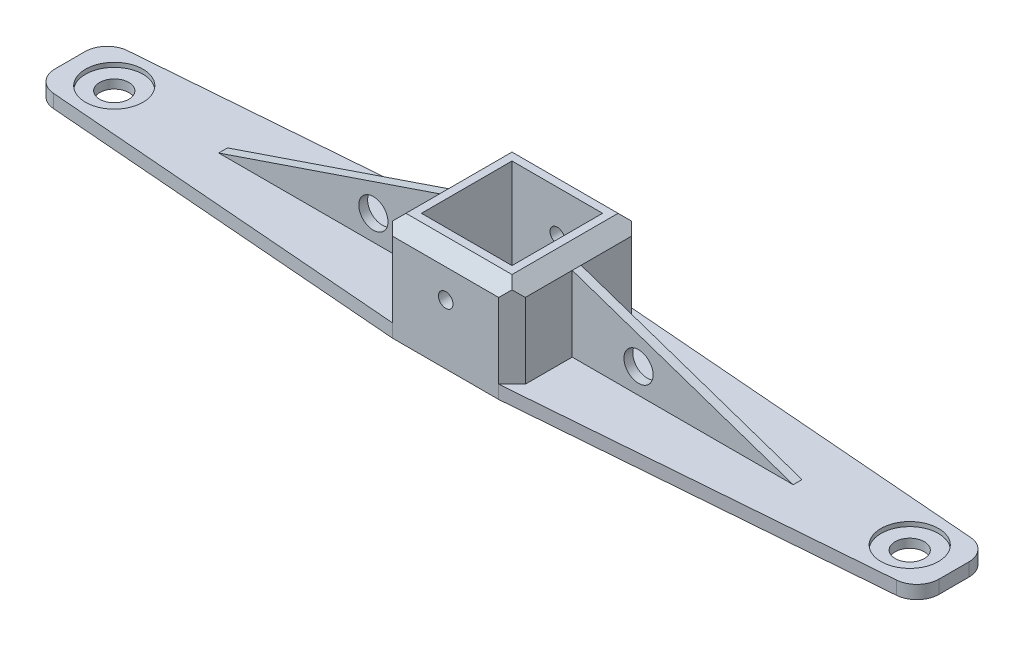
SolidWorks part; units mm, degrees
ref_plane "Front Plane" through (0, 0, 0) normal (0, 0, 1) x (1, 0, 0)
ref_plane "Top Plane" through (0, 0, 0) normal (0, 1, 0) x (1, 0, 0)
ref_plane "Right Plane" through (0, 0, 0) normal (1, 0, 0) x (0, 0, -1)
sketch "Sketch1" plane through (0, 0, 0) normal (0, 1, 0) x (1, 0, 0)
  line L1 (-100, 15) -> (100, 15)
  line L2 (-100, 15) -> (-100, -15)
  line L3 (-100, -15) -> (100, -15)
  line L4 (100, 15) -> (100, -15)
  line L5 (-100, 15) -> (100, -15) construction
  line L6 (-100, -15) -> (100, 15) construction
  point P0 (0, 0)
  dimension "D1" = 200
  dimension "D2" = 30
extrude "Boss-Extrude1" add sketch "Sketch1" along normal blind 3
sketch "Sketch2" plane through (0, 3, 0) normal (0, 1, 0) x (1, 0, 0)
  line L1 (-10.25, 10.25) -> (10.25, 10.25)
  line L2 (-10.25, 10.25) -> (-10.25, -10.25)
  line L3 (-10.25, -10.25) -> (10.25, -10.25)
  line L4 (10.25, 10.25) -> (10.25, -10.25)
  line L5 (-10.25, 10.25) -> (10.25, -10.25) construction
  line L6 (-10.25, -10.25) -> (10.25, 10.25) construction
  point P0 (0, 0)
  dimension "D1" = 20.5
  dimension "D2" = 20.5
extrude "Cut-Extrude1" cut sketch "Sketch2" against normal blind 3
sketch "Sketch3" plane through (0, 3, 0) normal (0, 1, 0) x (1, 0, 0)
  line L0 (100, 15) -> (-100, 15) construction
  line L1 (-10.25, -10.25) -> (10.25, -10.25)
  line L2 (-10.25, -10.25) -> (-10.25, 10.25)
  line L3 (-10.25, 10.25) -> (10.25, 10.25)
  line L4 (10.25, -10.25) -> (10.25, 10.25)
  line L5 (-10.25, -10.25) -> (10.25, 10.25) construction
  line L6 (-10.25, 10.25) -> (10.25, -10.25) construction
  line L7 (-15, -15) -> (15, -15)
  line L8 (-15, -15) -> (-15, 15)
  line L9 (-15, 15) -> (15, 15)
  line L10 (15, -15) -> (15, 15)
  line L11 (-15, -15) -> (15, 15) construction
  line L12 (-15, 15) -> (15, -15) construction
  point P0 (0, 0)
  point P7 (0, 0)
extrude "Boss-Extrude2" add sketch "Sketch3" along normal blind 20
chamfer "Chamfer1" distance 3 angle 45 4 edges at (-15, 13, 15) (-15, 13, -15) (15, 13, -15) (15, 13, 15)
sketch "Sketch4" plane through (0, 0, 15) normal (0, 0, 1) x (1, 0, 0)
  circle A0 centre (0, 13.5147) radius 1.65
  dimension "D1" = 3.3
extrude "Cut-Extrude2" cut sketch "Sketch4" against normal blind 40
chamfer "Chamfer2" distance 3 angle 45 4 edges at (0, 23, -15) (15, 23, 0) (0, 23, 15) (-15, 23, 0)
sketch "Sketch5" plane through (0, 3, 0) normal (0, 1, 0) x (1, 0, 0)
  line L0 (-12, 15) -> (-100, 8)
  line L1 (-100, 15) -> (-100, -15) construction
  line L2 (-100, 8) -> (-100, 15)
  line L3 (-100, 15) -> (-12, 15)
  line L4 (-12, -15) -> (-100, -15)
  line L5 (-100, -15) -> (-100, -8)
  line L6 (-100, -8) -> (-12, -15)
  line L7 (12, 15) -> (100, 15)
  line L8 (100, 15) -> (100, 8)
  line L9 (100, -15) -> (100, 15) construction
  line L10 (100, 8) -> (12, 15)
  line L11 (12, -15) -> (100, -15)
  line L12 (100, -15) -> (100, -8)
  line L13 (100, -8) -> (12, -15)
  dimension "D1" = 7
  dimension "D2" = 7
  dimension "D3" = 7
  dimension "D4" = 7
extrude "Cut-Extrude3" cut sketch "Sketch5" against normal blind 40
sketch "Sketch6" plane through (0, 3, 0) normal (0, 1, 0) x (1, 0, 0)
  line L0 (-15, 12) -> (-15, -12) construction
  line L1 (-15, 0.6316) -> (-65, 0.6316)
  line L2 (-15, 0.6316) -> (-15, -1.3684)
  line L3 (-15, -1.3684) -> (-65, -1.3684)
  line L4 (-65, 0.6316) -> (-65, -1.3684)
  line L5 (15, 12) -> (15, -12) construction
  line L6 (15, 0.6316) -> (65, 0.6316)
  line L7 (15, 0.6316) -> (15, -1.3684)
  line L8 (15, -1.3684) -> (65, -1.3684)
  line L9 (65, 0.6316) -> (65, -1.3684)
  point P12 (-15, -0.3684)
  point P13 (15, -0.3684)
  dimension "D1" = 50
  dimension "D2" = 50
  dimension "D3" = 1
  dimension "D4" = 1
extrude "Boss-Extrude3" add sketch "Sketch6" along normal blind 17
sketch "Sketch7" plane through (0, 0, 1.3684) normal (0, 0, 1) x (1, 0, 0)
  line L0 (-15, 20) -> (-65, 3)
  line L1 (-65, 3) -> (-71.3886, 29.5208)
  line L2 (-71.3886, 29.5208) -> (-15, 20)
  line L3 (15, 20) -> (65, 3)
  line L4 (65, 3) -> (84.4133, 43.1356)
  line L5 (84.4133, 43.1356) -> (15, 20)
extrude "Cut-Extrude4" cut sketch "Sketch7" against normal blind 17
sketch "Sketch8" plane through (0, 0, 1.3684) normal (0, 0, 1) x (1, 0, 0)
  line L0 (-15, 20) -> (-15, 3) construction
  line L1 (15, 20) -> (15, 3) construction
  circle A0 centre (-30, 8.6593) radius 3.302
  circle A1 centre (30, 8.6593) radius 3.302
  dimension "D1" = 6.604
  dimension "D2" = 6.604
  dimension "D3" = 15
  dimension "D4" = 15
extrude "Cut-Extrude5" cut sketch "Sketch8" against normal blind 17
sketch "Sketch9" plane through (0, 3, 0) normal (0, 1, 0) x (1, 0, 0)
  line L0 (-100, 8) -> (-100, -8) construction
  line L1 (100, -8) -> (100, 8) construction
  circle A0 centre (-90, 0) radius 3.302
  circle A1 centre (90, 0) radius 3.302
  dimension "D1" = 6.604
  dimension "D2" = 10
  dimension "D3" = 6.604
  dimension "D4" = 10
extrude "Cut-Extrude6" cut sketch "Sketch9" against normal blind 17
sketch "Sketch10" plane through (0, 3, 0) normal (0, 1, 0) x (1, 0, 0)
  circle A0 centre (90, 0) radius 6.5
  dimension "D1" = 13
extrude "Cut-Extrude7" cut sketch "Sketch10" against normal blind 1
sketch "Sketch11" plane through (0, 3, 0) normal (0, 1, 0) x (1, 0, 0)
  circle A0 centre (-90, 0) radius 6.5
  dimension "D1" = 13
extrude "Cut-Extrude8" cut sketch "Sketch11" against normal blind 1
fillet "Fillet1" radius 5 4 edges at (100, 1.5, -8) (100, 1.5, 8) (-100, 1.5, -8) (-100, 1.5, 8)
